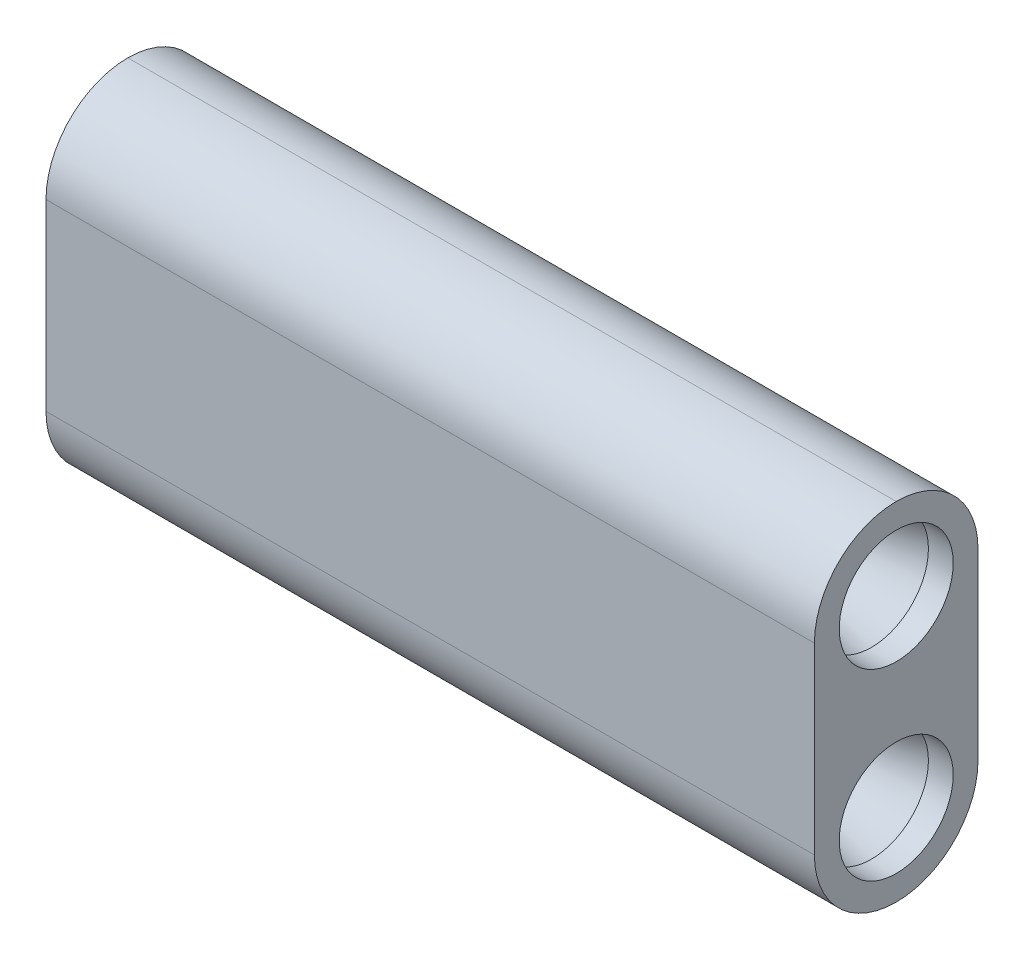
SolidWorks part; units mm, degrees
ref_plane "Front Plane" through (0, 0, 0) normal (0, 0, 1) x (1, 0, 0)
ref_plane "Top Plane" through (0, 0, 0) normal (0, 1, 0) x (1, 0, 0)
ref_plane "Right Plane" through (0, 0, 0) normal (1, 0, 0) x (0, 0, -1)
sketch "Sketch1" plane through (0, 0, 0) normal (0, 0, 1) x (1, 0, 0)
  line L1 (0, 0) -> (31, 0)
  line L2 (0, 0) -> (0, 14)
  line L3 (0, 14) -> (31, 14)
  line L4 (31, 0) -> (31, 14)
  dimension "D1" = 14
  dimension "D2" = 31
extrude "Boss-Extrude1" add sketch "Sketch1" along normal blind 6.6
sketch "Sketch2" plane through (0, 0, 0) normal (-1, 0, 0) x (0, 0, 1)
  line L0 (6.6, 0) -> (0, 0) construction
  line L1 (6.6, 14) -> (6.6, 0) construction
  line L4 (6.6, 14) -> (0, 14) construction
  circle A0 centre (3.3, 10.7) radius 2.3
  circle A1 centre (3.3, 3.3) radius 2.3
  dimension "D1" = 4.6
  dimension "D2" = 4.6
  dimension "D3" = 3.3
  dimension "D4" = 3.3
  dimension "D6" = 3.3
  dimension "D5" = 3.3
extrude "Cut-Extrude1" cut sketch "Sketch2" against normal blind 1 contours A1 | A0
fillet "Zaoblit7" radius 3.3 1 edges at (15.5, 14, 0) type face fillet first side face at (15.5, 14, 3.3) second side face at (15.5, 7, 0)
fillet "Zaoblit12" radius 3.3 1 edges at (15.5, 14, 6.6) type face fillet first side face at (15.5, 14, 4.95) second side face at (15.5, 7, 6.6)
fillet "Zaoblit13" radius 3.3 1 edges at (15.5, 0, 6.6) type face fillet first side face at (15.5, 5.35, 6.6) second side face at (15.5, 0, 3.3)
fillet "Zaoblit14" radius 3.3 1 edges at (15.5, 0, 0) type face fillet first side face at (15.5, 5.35, 0) second side face at (15.5, 0, 1.65)
sketch "Skica1" plane through (31, 0, 0) normal (1, 0, 0) x (0, 0, -1)
  line L2 (-6.6, 3.3) -> (-6.6, 10.7) construction
  circle A0 centre (-3.3, 10.7) radius 2.3
  circle A1 centre (-3.3, 3.3) radius 2.3
  dimension "D1" = 4.6
  dimension "D2" = 4.6
  dimension "D3" = 3.3
  dimension "D4" = 3.3
  dimension "D6" = 3.3
  dimension "D5" = 3.3
extrude "Odebrat vysunutím1" cut sketch "Skica1" against normal blind 1
sketch "Skica3" plane through (1, 0, 0) normal (-1, 0, 0) x (0, 0, 1)
  circle A0 centre (3.3, 10.7) radius 2.3
  circle A1 centre (3.3, 10.7) radius 2.3 construction
  dimension "D1" = 4.6
  dimension "D2" = 0
  dimension "D3" = 0
extrude "Odebrat vysunutím2" cut sketch "Skica3" against normal blind 3 draft 15
sketch "Skica4" plane through (1, 0, 0) normal (-1, 0, 0) x (0, 0, 1)
  circle A0 centre (3.3, 3.3) radius 2.3
  circle A1 centre (3.3, 3.3) radius 2.3 construction
  dimension "D1" = 4.6
  dimension "D2" = 0
extrude "Odebrat vysunutím3" cut sketch "Skica4" against normal blind 3 draft 15
sketch "Skica5" plane through (30, 0, 0) normal (1, 0, 0) x (0, 0, -1)
  circle A0 centre (-3.3, 10.7) radius 2.3
  circle A1 centre (-3.3, 10.7) radius 2.3 construction
  dimension "D1" = 4.6
  dimension "D2" = 0
extrude "Odebrat vysunutím4" cut sketch "Skica5" against normal blind 3 draft 15
sketch "Skica6" plane through (30, 0, 0) normal (1, 0, 0) x (0, 0, -1)
  circle A0 centre (-3.3, 3.3) radius 2.3
  circle A1 centre (-3.3, 3.3) radius 2.3 construction
  circle A2 centre (-3.3, 3.3) radius 2.3 construction
  dimension "D1" = 4.6
  dimension "D2" = 0
  dimension "D3" = 0
extrude "Odebrat vysunutím5" cut sketch "Skica6" against normal blind 3 draft 15
